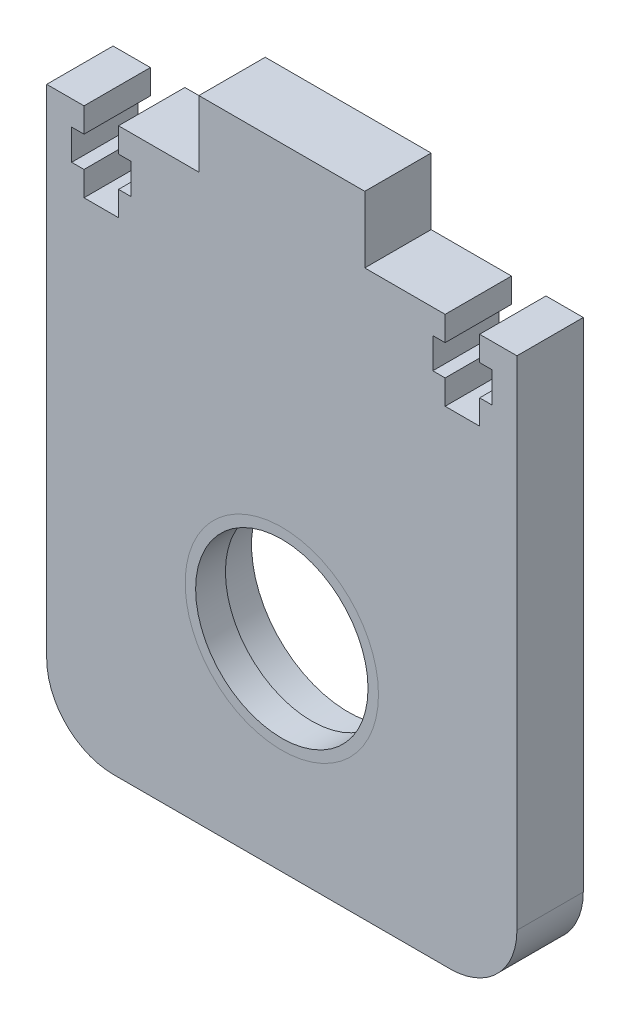
SolidWorks part; units mm, degrees
ref_plane "Front Plane" through (0, 0, 0) normal (0, 0, 1) x (1, 0, 0)
ref_plane "Top Plane" through (0, 0, 0) normal (0, 1, 0) x (1, 0, 0)
ref_plane "Right Plane" through (0, 0, 0) normal (1, 0, 0) x (0, 0, -1)
sketch "Sketch12" plane through (0, 0, 0) normal (0, 0, 1) x (1, 0, 0)
  line L0 (62.1258, 0) -> (62.1258, 108.03)
  line L1 (62.1258, 108.03) -> (152.1258, 108.03)
  line L2 (62.1258, 0) -> (152.1258, 0)
  line L3 (152.1258, 108.03) -> (152.1258, 0)
  circle A0 centre (99.6258, 37.5) radius 25.4
  circle A1 centre (99.6258, 37.5) radius 6.5
  dimension "D3" = 50.8
  dimension "D4" = 13
  dimension "D1" = 108.03
  dimension "D2" = 90
extrude "Boss-Extrude10" add sketch "Sketch12" along normal blind 12.7 separate body contours L1 L3 L2 L0
sketch "Sketch15" plane through (0, 0, 12.7) normal (0, 0, 1) x (1, 0, 0)
  line L0 (62.1258, 0) -> (152.1258, 0) construction
  circle A0 centre (107.1258, 38.6276) radius 25.4
  point P2 (0, 0)
  point P3 (0, 0)
  point P4 (0, 0)
  point P7 (107.1258, 0)
  dimension "D1" = 50.8
  dimension "D2" = 38.6276
sketch "Sketch24" plane through (0, 0, 12.7) normal (0, 0, 1) x (1, 0, 0)
  line L0 (62.1258, 108.03) -> (62.1258, 104.03)
  line L1 (62.1258, 0) -> (62.1258, 108.03) construction
  line L2 (62.1258, 104.03) -> (152.1258, 104.03)
  line L3 (152.1258, 108.03) -> (152.1258, 0) construction
  line L4 (152.1258, 104.03) -> (152.1258, 108.03)
  line L5 (152.1258, 108.03) -> (62.1258, 108.03)
  dimension "D1" = 4
sketch "Sketch25" plane through (0, 0, 12.7) normal (0, 0, 1) x (1, 0, 0)
  circle A0 centre (107.1258, 38.6276) radius 18.5
  dimension "D1" = 37
extrude "Cut-Extrude1" cut sketch "Sketch25" against normal through all
sketch "Sketch26" plane through (0, 0, 12.7) normal (0, 0, 1) x (1, 0, 0)
  circle A0 centre (107.1258, 38.6276) radius 16.5
  circle A1 centre (107.1258, 38.6276) radius 18.5
  dimension "D1" = 37
  dimension "D2" = 2
extrude "Boss-Extrude15" add sketch "Sketch26" against normal blind 5.7 separate body
fillet "Fillet1" radius 12.8 2 edges at (152.1258, 0, 6.35) (62.1258, 0, 6.35)
sketch "Sketch27" plane through (0, 0, 0) normal (0, 0, -1) x (-1, 0, 0)
  line L0 (-69.2638, 108.03) -> (-69.2638, 103.331)
  line L1 (-152.1258, 108.03) -> (-62.1258, 108.03) construction
  line L2 (-69.2638, 103.331) -> (-66.9018, 103.331)
  line L3 (-66.9018, 103.331) -> (-66.9018, 97.489)
  line L4 (-66.9018, 97.489) -> (-69.2638, 97.489)
  line L5 (-69.2638, 97.489) -> (-69.2638, 92.79)
  line L6 (-69.2638, 92.79) -> (-75.8678, 92.79)
  line L7 (-75.8678, 92.79) -> (-75.8678, 97.489)
  line L8 (-75.8678, 97.489) -> (-78.2298, 97.489)
  line L9 (-78.2298, 97.489) -> (-78.2298, 103.331)
  line L10 (-78.2298, 103.331) -> (-75.8678, 103.331)
  line L11 (-75.8678, 103.331) -> (-75.8678, 108.03)
  line L12 (-75.8678, 108.03) -> (-69.2638, 108.03)
  line L13 (-138.3838, 103.331) -> (-138.3838, 108.03)
  line L15 (-107.1258, 108.03) -> (-107.1258, 67.3255)
  line L28 (-136.0218, 103.331) -> (-138.3838, 103.331)
  line L29 (-136.0218, 97.489) -> (-136.0218, 103.331)
  line L30 (-138.3838, 97.489) -> (-136.0218, 97.489)
  line L31 (-138.3838, 92.79) -> (-138.3838, 97.489)
  line L32 (-144.9878, 92.79) -> (-138.3838, 92.79)
  line L33 (-144.9878, 97.489) -> (-144.9878, 92.79)
  line L34 (-147.3498, 97.489) -> (-144.9878, 97.489)
  line L35 (-147.3498, 103.331) -> (-147.3498, 97.489)
  line L36 (-144.9878, 103.331) -> (-147.3498, 103.331)
  line L37 (-144.9878, 108.03) -> (-144.9878, 103.331)
  line L38 (-138.3838, 108.03) -> (-144.9878, 108.03)
  point P22 (-72.5658, 108.03)
  point P29 (-141.6858, 108.03)
  line M19 (-62.1258, 108.03) -> (-152.1258, 108.03)
  dimension "D1" = 6.604
  dimension "D2" = 11.328
  dimension "D3" = 5.842
  dimension "D4" = 15.24
  dimension "D5" = 69.12
ref_axis "Axis2" through (107.1258, 108.03, 0) along (0, -1, 0)
extrude "Cut-Extrude2" cut sketch "Sketch27" against normal through all contours L11 L10 L9 L8 L7 L6 L5 L4 L3 L2 L0 M19 | L37 L36 L35 L34 L33 L32 L31 L30 L29 L28 L13 M19 region at (141.6858, 100.41, 0) region at (72.5658, 100.41, 0)
sketch "Sketch28" plane through (0, 108.03, 0) normal (0, 1, 0) x (1, 0, 0)
  line L0 (107.1258, 0) -> (91.2508, 0)
  line L1 (75.8678, 0) -> (138.3838, 0) construction
  line L2 (91.2508, 0) -> (91.2508, -12.7)
  line L3 (81.7258, -12.7) -> (132.5258, -12.7) construction
  line L4 (91.2508, -12.7) -> (123.0008, -12.7)
  line L5 (123.0008, -12.7) -> (123.0008, 0)
  line L6 (123.0008, 0) -> (107.1258, 0)
  dimension "D1" = 31.75
extrude "Boss-Extrude16" add sketch "Sketch28" along normal blind 12.7
